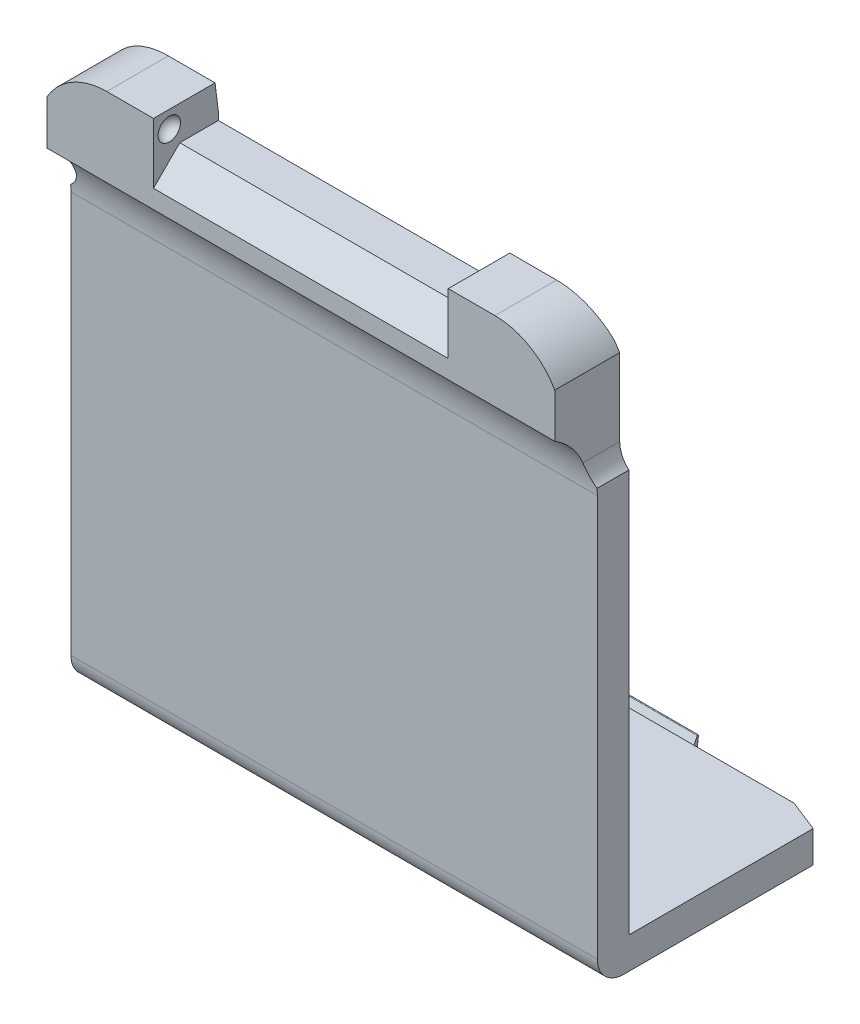
SolidWorks part; units mm, degrees
ref_plane "Front Plane" through (0, 0, 0) normal (0, 0, 1) x (1, 0, 0)
ref_plane "Top Plane" through (0, 0, 0) normal (0, 1, 0) x (1, 0, 0)
ref_plane "Right Plane" through (0, 0, 0) normal (1, 0, 0) x (0, 0, -1)
sketch "Sketch1" plane through (0, 0, 0) normal (0, 0, 1) x (1, 0, 0)
  line L1 (0, 0) -> (40, 0)
  line L2 (0, 0) -> (0, 40.6)
  line L3 (0, 40.6) -> (40, 40.6)
  line L4 (40, 0) -> (40, 40.6)
  dimension "D1" = 40
  dimension "D2" = 40.6
extrude "Boss-Extrude1" add sketch "Sketch1" along normal blind 2.4
sketch "Sketch2" plane through (0, 0, 2.4) normal (0, 0, 1) x (1, 0, 0)
  line L1 (0, 0) -> (40, 0)
  line L2 (0, 0) -> (0, -2.4)
  line L3 (0, -2.4) -> (40, -2.4)
  line L4 (40, 0) -> (40, -2.4)
  dimension "D1" = 2.4
extrude "Boss-Extrude2" add sketch "Sketch2" against normal blind 17.35
sketch "Sketch3" plane through (0, 0, 2.4) normal (0, 0, 1) x (1, 0, 0)
  line L0 (40, 40.6) -> (0, 40.6) construction
  line L1 (8.8, 40.6) -> (31.2, 40.6)
  line L2 (8.8, 40.6) -> (8.8, 38)
  line L3 (8.8, 38) -> (31.2, 38)
  line L4 (31.2, 40.6) -> (31.2, 38)
  line L5 (8.8, 38) -> (0, 40.6) construction
  line L6 (31.2, 38) -> (40, 40.6) construction
  dimension "D1" = 22.4
  dimension "D2" = 2.6
extrude "Cut-Extrude1" cut sketch "Sketch3" against normal up to surface (2.4 mm away) up to face at (15, 20.3, 0)
ref_plane "Plane1" through (20, 0, 0) normal (-1, 0, 0) x (0, 0, 1)
sketch "Sketch5" plane through (0, 0, 2.4) normal (0, 0, 1) x (1, 0, 0)
  line L0 (0, 34.6) -> (40, 34.6)
  line L8 (40, 40.6) -> (31.2, 40.6)
  line L9 (31.2, 40.6) -> (31.2, 38)
  line L10 (31.2, 38) -> (8.8, 38)
  line L11 (8.8, 38) -> (8.8, 40.6)
  line L12 (8.8, 40.6) -> (0, 40.6)
  line L13 (0, 40.6) -> (0, -2.4)
  line L14 (0, -2.4) -> (40, -2.4)
  line L15 (40, -2.4) -> (40, 40.6)
  line L16 (40, 40.6) -> (31.2, 40.6)
  line L17 (31.2, 40.6) -> (31.2, 38)
  line L18 (31.2, 38) -> (8.8, 38)
  line L19 (8.8, 38) -> (8.8, 40.6)
  line L20 (8.8, 40.6) -> (0, 40.6)
  line L21 (0, 40.6) -> (0, -2.4)
  line L22 (0, -2.4) -> (40, -2.4)
  line L23 (40, -2.4) -> (40, 40.6)
  line M10 (40, 40.6) -> (31.2, 40.6)
  line M11 (31.2, 40.6) -> (31.2, 38)
  line M12 (31.2, 38) -> (8.8, 38)
  line M13 (8.8, 38) -> (8.8, 40.6)
  line M14 (8.8, 40.6) -> (0, 40.6)
  line M15 (0, 40.6) -> (0, -2.4)
  line M17 (40, -2.4) -> (40, 40.6)
  dimension "D2" = 6
  dimension "D1" = 0
extrude "Boss-Extrude3" add sketch "Sketch5" along normal blind 2.53 contours L0 M15 M17 M10 M11 M12 M13 M14 region at (20, 37.0553, 2.4)
sketch "Sketch4" plane through (8.8, 0, 0) normal (1, 0, 0) x (0, 0, -1)
  line L3 (-2.88, 39.3) -> (-4.58, 39.3)
  line L4 (-4.93, 38) -> (-4.93, 40.6) construction
  arc A0 (-4.58, 39.3) -> (-2.88, 39.3) centre (-3.73, 39.3) ccw
  dimension "D1" = 1.7
  dimension "D2" = 1.2
revolve "Cut-Revolve2" cut sketch "Sketch4" angle 360 about L3
mirror "Mirror2" about plane through (20, 0, 0) normal (-1, 0, 0) of "Cut-Revolve2"
fillet "Fillet1" radius 5.25 2 edges at (0, 40.6, 2.465) (40, 40.6, 2.465)
fillet "Fillet2" radius 5.25 1 edges
sketch "Sketch6" plane through (31.2, 0, 0) normal (-1, 0, 0) x (0, 0, 1)
  line L0 (0, 40.6) -> (0, 38.6)
  line L1 (0, 40.6) -> (4.93, 40.6) construction
  line L2 (0.25, 40.6) -> (0, 40.6)
  line L4 (0, 38) -> (0, 40.6) construction
  line L5 (0, 38.6) -> (0.25, 40.6)
  dimension "D1" = 0.25
  dimension "D2" = 2
extrude "Cut-Extrude2" cut sketch "Sketch6" against normal blind 16.4
mirror "Mirror3" about plane through (20, 0, 0) normal (-1, 0, 0) of "Cut-Extrude2"
fillet "Fillet3" radius 2 1 edges at (20, -2.4, 2.4)
sketch "Sketch7" plane through (0, 0, 0) normal (0, 1, 0) x (1, 0, 0)
  line L0 (37.6, 14.952) -> (40, 14)
  line L1 (40, 14) -> (36.1823, 15.5144) construction
  line L2 (40, 14) -> (37.6, 14.952) construction
  line L3 (40, 14) -> (40, 14.95)
  line L4 (40, 14.95) -> (37.6, 14.952)
extrude "Cut-Extrude3" cut sketch "Sketch7" against normal through all
ref_plane "Plane2" through (20, 0, 0) normal (-1, 0, 0) x (0, 0, 1)
sketch "Sketch8" plane through (20, 0, 0) normal (-1, 0, 0) x (0, 0, 1)
  line L0 (-14.95, 0) -> (-15.323, 0.8)
  line L1 (-15.323, 0.8) -> (-14.95, -2.4)
  line L2 (-14.95, -2.4) -> (-14.95, 0)
  dimension "D1" = 155
  dimension "D2" = 0.8
extrude "Boss-Extrude4" add sketch "Sketch8" along normal blind 10 and the other way blind 10
fillet "Fillet4" radius 0.05 1 edges at (20, 0.8, -15.323)
chamfer "Chamfer1" distance 2 angle 45 1 edges at (20, 38, 4.93)
sketch "Sketch9" plane through (0, 0, 0) normal (0, 0, -1) x (-1, 0, 0)
  line L0 (-40, 0) -> (-40, 35.35) construction
  line L1 (-40, 30.6) -> (-39.3, 30.6)
  line L2 (-40, 30.6) -> (-40, 40.6)
  line L3 (-40, 40.6) -> (-39.3, 40.6)
  line L4 (-39.3, 30.6) -> (-39.3, 40.6)
  line L5 (-34.75, 40.6) -> (-31.2, 40.6) construction
  line L6 (-20, 38) -> (-20, 30.6) construction
  line L7 (-8.8, 38) -> (-31.2, 38) construction
  line L8 (-0.7, 30.6) -> (-0.7, 40.6)
  line L9 (0, 40.6) -> (-0.7, 40.6)
  line L10 (0, 30.6) -> (0, 40.6)
  line L11 (0, 30.6) -> (-0.7, 30.6)
  dimension "D1" = 0.7
  dimension "D2" = 10
extrude "Cut-Extrude4" cut sketch "Sketch9" against normal through all
fillet "Fillet5" radius 2 2 edges at (0.7, 30.6, 1.2115) (39.3, 30.6, 1.2115)
